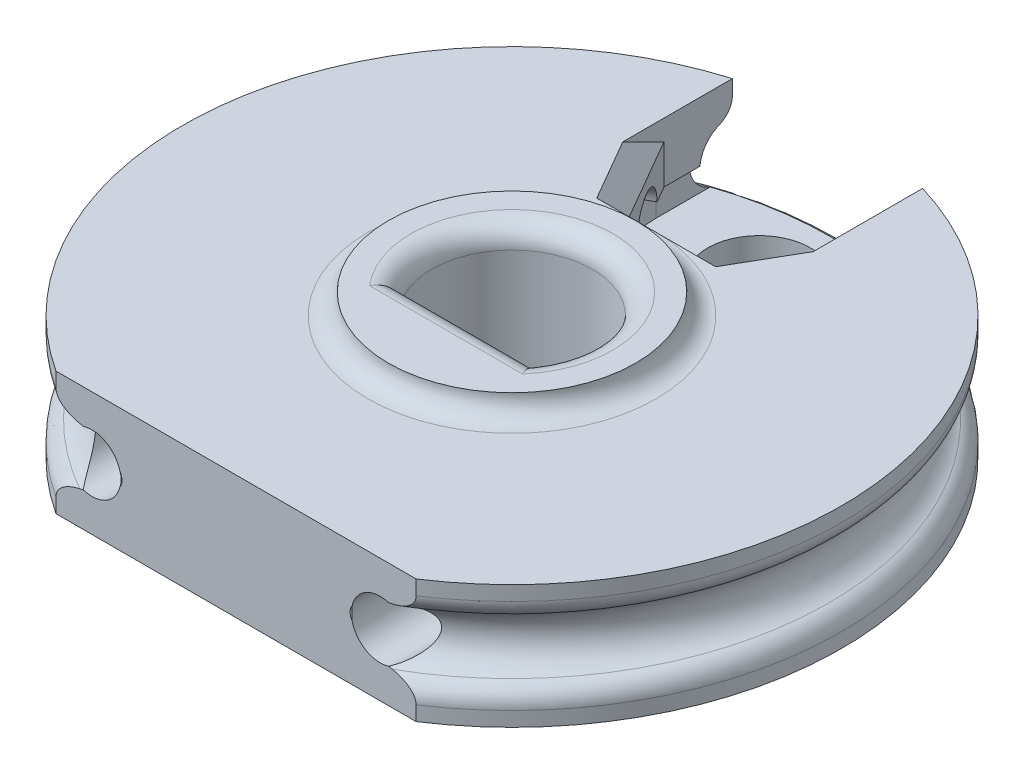
SolidWorks part; units mm, degrees
ref_plane "Front Plane" through (0, 0, 0) normal (0, 0, 1) x (1, 0, 0)
ref_plane "Top Plane" through (0, 0, 0) normal (0, 1, 0) x (1, 0, 0)
ref_plane "Right Plane" through (0, 0, 0) normal (1, 0, 0) x (0, 0, -1)
sketch "Sketch1" plane through (0, 0, 0) normal (0, 1, 0) x (1, 0, 0)
  line L0 (-1.6101, -1.1) -> (1.6101, -1.1)
  arc A0 (1.6101, -1.1) -> (-1.6101, -1.1) centre (0, 0) ccw
  circle A1 centre (0, 0) radius 8
  arc A2 (-1.6101, -1.1) -> (1.6101, -1.1) centre (0, 0) ccw construction
  dimension "D1" = 16
  dimension "D2" = 3.9
  dimension "D3" = 1.1
extrude "Boss-Extrude1" add sketch "Sketch1" along normal blind 3
sketch "Sketch2" plane through (0, 0, 0) normal (0, 0, 1) x (1, 0, 0)
  line L0 (-8, 0.75) -> (-8, 2.25)
  line L1 (-8, 3) -> (-8, 0) construction
  line L2 (-8, 1.5) -> (-7.25, 1.5) construction
  ellipse E0 centre (-8, 1.5) end of major axis (-8.75, 1.5) minor radius 0.75 (-8, 0.75) -> (-8, 2.25) ccw
  point P5 (-8, 1.5)
  dimension "D1" = 1.5
  dimension "D2" = 0.75
revolve "Cut-Revolve1" cut sketch "Sketch2" angle 360 about axis through (0, 3, 0) along (0, -1, 0)
sketch "Sketch3" plane through (0, 3, 0) normal (0, 1, 0) x (1, 0, 0)
  line L0 (0, 0) -> (-4, -6.9282) construction
  line L1 (0, 0) -> (4, -6.9282) construction
  line L2 (0, 0) -> (0, -8) construction
  line L3 (-2.5981, -4.5) -> (2.0981, -4.5) construction
  line L4 (-2.5981, -4) -> (2.5981, -4)
  line L5 (-2.5981, -5) -> (2.5981, -5)
  line L6 (2.0981, -4.5) -> (2.5981, -4.5) construction
  circle A0 centre (0, 0) radius 8 construction
  arc A1 (-2.5981, -4) -> (-2.5981, -5) centre (-2.5981, -4.5) ccw
  arc A2 (2.5981, -5) -> (2.5981, -4) centre (2.5981, -4.5) ccw
  arc A3 (-2.0981, -4.5) -> (-2.3481, -4.067) centre (-2.5981, -4.5) ccw construction
  arc A4 (-2.5981, -5) -> (-2.0981, -4.5) centre (-2.5981, -4.5) ccw construction
  arc A5 (2.0981, -4.5) -> (2.5981, -5) centre (2.5981, -4.5) ccw construction
  arc A6 (2.3481, -4.067) -> (2.0981, -4.5) centre (2.5981, -4.5) ccw construction
  arc A7 (2.5981, -4) -> (2.3481, -4.067) centre (2.5981, -4.5) ccw construction
  arc A8 (-2.3481, -4.067) -> (-2.5981, -4) centre (-2.5981, -4.5) ccw construction
  dimension "D4" = 1
  dimension "D5" = 1
  dimension "D1" = 30
  dimension "D2" = 30
  dimension "D3" = 4.5
extrude "Cut-Extrude1" [suppressed] cut sketch "Sketch3" against normal blind 2.25
sketch3d "3DSketch1"
  line L0 (-4, 3, 6.9282) -> (-4, 6.6587, 6.9282) construction
  line L1 (-4, 6.6587, 6.9282) -> (-2.1356, 6.6587, 8.0046) construction
  line L2 (0, 3, 0) -> (-4, 3, 6.9282) construction
  line L3 (4, 3, 6.9282) -> (4, 5.9313, 6.9282) construction
  line L4 (4, 3, 6.9282) -> (7.5555, 3, 4.8754) construction
  line L6 (0, 3, 0) -> (4, 3, 6.9282) construction
ref_plane "Plane1" through (-4, 0, 6.9282) normal (-0.5, 0, 0.866) x (0.866, 0, 0.5)
ref_plane "Plane2" through (4, 0, 6.9282) normal (0.5, 0, 0.866) x (0.866, 0, -0.5)
sketch "Sketch8" plane through (0, 3, 0) normal (0, -1, 0) x (1, 0, 0)
  line L0 (1.6101, 1.1) -> (-1.6101, 1.1)
  circle A0 centre (0, 0) radius 3
  arc A1 (-1.6101, 1.1) -> (1.6101, 1.1) centre (0, 0) ccw
  arc A2 (1.6101, 1.1) -> (-1.6101, 1.1) centre (0, 0) ccw construction
  dimension "D1" = 6
extrude "Boss-Extrude2" add sketch "Sketch8" against normal blind 0.5
fillet "Fillet1" radius 0.5 5 edges at (0, 3, 3) (0, 3.5, 1.1) (0, 0, 1.1) (0, 3.5, -1.95) (0, 0, -1.95)
sketch "Sketch9" plane through (0, 3, 0) normal (0, 1, 0) x (1, 0, 0)
  line L0 (0, 0) -> (0, 8) construction
  line L1 (-1.1547, 4) -> (1.1547, 4)
  line L2 (-1.1547, 8) -> (1.1547, 8)
  line L3 (-1.1547, 4) -> (-2.3094, 6)
  line L4 (-2.3094, 6) -> (-1.1547, 8)
  line L5 (1.1547, 8) -> (2.3094, 6)
  line L6 (2.3094, 6) -> (1.1547, 4)
  line L7 (2.3094, 6) -> (2.3094, 8)
  line L8 (-2.3094, 6) -> (-2.3094, 8)
  line L9 (-2.3094, 8) -> (-1.1547, 8)
  line L10 (1.1547, 8) -> (2.3094, 8)
  circle A0 centre (0, 0) radius 8 construction
  circle A1 centre (0, 0) radius 7.25 construction
  circle A2 centre (0, 6) radius 1.25 construction
  circle A3 centre (0, 6) radius 2.5 construction
  circle A4 centre (0, 6) radius 2.3094 construction
  circle M4 centre (0, 0) radius 8
  dimension "D1" = 14.5
  dimension "D2" = 2.5
  dimension "D3" = 5
  dimension "D4" = 4
ref_plane "Plane3" through (0, 0.8, 0) normal (0, 1, 0) x (1, 0, 0)
sketch "Sketch10" plane through (0, 0.8, 0) normal (0, 1, 0) x (1, 0, 0)
  line L0 (-2.5, 6) -> (-2.5, 8.5)
  line L5 (2.5, 6) -> (2.5, 8.5)
  line L10 (-2.5, 8.5) -> (2.5, 8.5)
  arc A0 (-2.5, 6) -> (2.5, 6) centre (0, 6) ccw
  arc A1 (0, 8.5) -> (-2.5, 6) centre (0, 6) ccw construction
  arc A2 (2.5, 6) -> (0, 8.5) centre (0, 6) ccw construction
  dimension "D1" = 5
extrude "Cut-Extrude4" cut sketch "Sketch10" along normal blind 0.75
extrude "Cut-Extrude5" cut sketch "Sketch9" against normal blind 1.75 contours L6 L5 L4 L3 L1 M4 | L5 L2 M4 | L4 L2 M4 | L10 L5 L7 M4 | L5 L7 M4 | L8 L4 M4 | L9 L8 L4 M4 region at (0, 3, -5.9902) region at (-1.9392, 3, -7.199) region at (1.9392, 3, -7.199) region at (-1.8639, 3, -7.8868) region at (-0.886, 3, -7.9727) region at (0.886, 3, -7.9727) region at (1.8639, 3, -7.8868)
chamfer "Chamfer1" distance 0.5 angle 45 3 edges at (1.7321, 3, -5) (-1.7321, 3, -5) (0, 3, -4)
sketch "Sketch11" plane through (0, 0.8, 0) normal (0, 1, 0) x (1, 0, 0)
  circle A0 centre (0, 6) radius 1.25
  dimension "D1" = 2.5
extrude "Cut-Extrude6" cut sketch "Sketch11" against normal through all
fillet "Fillet2" radius 0.5 2 edges at (0, 2.25, 8) (0, 0.75, 8)
ref_plane "Plane4" through (0, 1.5, 0) normal (0, -1, 0) x (-1, 0, 0)
sketch "Sketch12" plane through (0, 1.5, 0) normal (0, -1, 0) x (-1, 0, 0)
  line L0 (-3.5, -8.0741) -> (-3.5, 2.4378)
  line L2 (-1.7321, 5) -> (-2.1651, 4.75)
  line L3 (-1.1547, 4) -> (-2.3094, 6) construction
  line L4 (-3.5, 2.4378) -> (-3.5, 1.5922) construction
  arc A0 (-2.1651, 4.75) -> (-3.5, 2.4378) centre (-0.8301, 2.4378) ccw
  point P5 (-1.9822, 4.8556)
  point P9 (-3.5, 1.5922)
  dimension "D1" = 3.5
  dimension "D2" = 0.5
sketch "Sketch13" plane through (0, 1.5, 0) normal (0, -1, 0) x (-1, 0, 0)
  line L0 (3.5, -8.3875) -> (3.5, 2.4378)
  line L1 (1.7321, 5) -> (2.1651, 4.75)
  line L2 (1.1547, 4) -> (2.3094, 6) construction
  arc A0 (2.1651, 4.75) -> (3.5, 2.4378) centre (0.8301, 2.4378) cw
  dimension "D1" = 0.5
  dimension "D2" = 3.5
sketch "Sketch14" plane through (-0.866, 0, -0.5) normal (-0.866, 0, -0.5) x (-0.5, 0, 0.866)
  line L0 (-3.9462, 0.8) -> (-6.4462, 0.8) construction
  circle A0 centre (-5.1962, 1.5) radius 0.7
sweep "Cut-Sweep1" cut profiles "Sketch14" path "Sketch12"
sketch "Sketch15" plane through (0.866, 0, -0.5) normal (0.866, 0, -0.5) x (-0.5, 0, -0.866)
  line L0 (6.4462, 0.8) -> (3.9462, 0.8) construction
  circle A0 centre (5.1962, 1.5) radius 0.7
sweep "Cut-Sweep2" cut profiles "Sketch15" path "Sketch13"
sketch "Sketch16" plane through (0, 3, 0) normal (0, 1, 0) x (1, 0, 0)
  line L1 (-5.231, -9.879) -> (5.231, -9.879)
  line L2 (-5.231, -9.879) -> (-5.231, -6.7)
  line L3 (-5.231, -6.7) -> (5.231, -6.7)
  line L4 (5.231, -9.879) -> (5.231, -6.7)
  arc A2 (-2.3094, 7.6594) -> (2.3094, 7.6594) centre (0, 0) ccw construction
  point P8 (0, -8)
  dimension "D1" = 1.3
extrude "Cut-Extrude7" cut sketch "Sketch16" against normal through all
